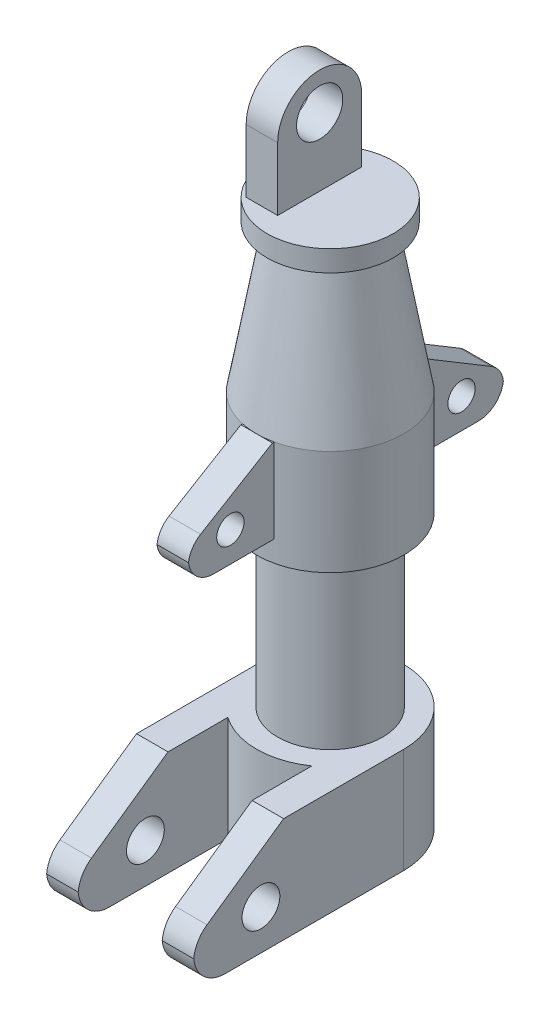
SolidWorks part; units mm, degrees
ref_plane "Front Plane" through (0, 0, 0) normal (0, 0, 1) x (1, 0, 0)
ref_plane "Top Plane" through (0, 0, 0) normal (0, 1, 0) x (1, 0, 0)
ref_plane "Right Plane" through (0, 0, 0) normal (1, 0, 0) x (0, 0, -1)
sketch "Sketch1" plane through (0, 0, 0) normal (0, 1, 0) x (1, 0, 0)
  circle A0 centre (0, 0) radius 35
  dimension "D1" = 70
ref_plane "Plane1" through (0, 50, 0) normal (0, 1, 0) x (1, 0, 0)
ref_plane "Plane2" through (0, 130, 0) normal (0, 1, 0) x (1, 0, 0)
ref_plane "Plane3" through (0, 180, 0) normal (0, 1, 0) x (1, 0, 0)
ref_plane "Plane4" through (0, 250, 0) normal (0, 1, 0) x (1, 0, 0)
extrude "Boss-Extrude1" add sketch "Sketch1" along normal blind 50 contours A0
sketch "Sketch6" plane through (0, 50, 0) normal (0, 1, 0) x (1, 0, 0)
  circle A0 centre (0, 0) radius 25
  dimension "D1" = 50
extrude "Boss-Extrude2" add sketch "Sketch6" along normal blind 80
sketch "Sketch7" plane through (0, 130, 0) normal (0, 1, 0) x (1, 0, 0)
  circle A0 centre (0, 0) radius 35
  dimension "D1" = 70
extrude "Boss-Extrude3" add sketch "Sketch7" along normal blind 50
ref_plane "Plane6" through (0, 250, 0) normal (0, 1, 0) x (1, 0, 0)
sketch "Sketch10" plane through (0, 250, 0) normal (0, 1, 0) x (1, 0, 0)
  circle A0 centre (0, 0) radius 30
  dimension "D1" = 60
extrude "Boss-Extrude5" add sketch "Sketch10" along normal blind 10 separate body
sketch "Sketch11" plane through (0, 0, 0) normal (1, 0, 0) x (0, 0, -1)
  line L0 (0, 250) -> (22.6571, 250)
  line L1 (-30, 250) -> (30, 250) construction
  line L2 (22.6571, 250) -> (35, 180)
  line L3 (35, 180) -> (0, 180)
  line L4 (35, 180) -> (-35, 180) construction
  line L5 (0, 180) -> (0, 250)
  dimension "D1" = 10
revolve "Revolve1" add sketch "Sketch11" angle 360 about L5
sketch "Sketch12" plane through (0, 0, 0) normal (0, -1, 0) x (1, 0, 0)
  line L0 (-35, 0) -> (-35, 100.0092)
  line L1 (-35, 100.0092) -> (35, 100.0092)
  line L2 (35, 100.0092) -> (35, 0)
  line L3 (35, 0) -> (-35, 0)
  circle A0 centre (0, 0) radius 35 construction
extrude "Boss-Extrude6" add sketch "Sketch12" against normal blind 50
sketch "Sketch13" plane through (-35, 0, 0) normal (-1, 0, 0) x (0, 0, 1)
  line L0 (57.1647, 50) -> (100.0092, 20)
  line L1 (100.0092, 50) -> (0, 50) construction
  line L2 (100.0092, 50) -> (100.0092, 0) construction
  line L4 (100.0092, 0) -> (0, 0) construction
  line L5 (57.1647, 50) -> (100.0092, 50)
  line L6 (100.0092, 50) -> (100.0092, 20)
  dimension "D1" = 35
  dimension "D2" = 20
extrude "Cut-Extrude1" cut sketch "Sketch13" against normal through all
sketch "Sketch14" plane through (0, 0, 0) normal (0, -1, 0) x (1, 0, 0)
  line L0 (-35, 100.0092) -> (-35, 0) construction
  line L1 (-20, 108.7406) -> (20, 108.7406)
  line L2 (-20, 108.7406) -> (-20, 28.7228)
  line L4 (20, 108.7406) -> (20, 28.7228)
  line L5 (35, 0) -> (35, 100.0092) construction
  arc A0 (20, 28.7228) -> (-20, 28.7228) centre (0, 0) ccw
  dimension "D1" = 70
  dimension "D2" = 15
  dimension "D3" = 15
extrude "Cut-Extrude2" cut sketch "Sketch14" against normal through all
fillet "Fillet1" radius 15 4 edges at (27.5, 0, 100.0092) (27.5, 20, 100.0092) (-27.5, 0, 100.0092) (-27.5, 20, 100.0092)
sketch "Sketch15" plane through (-35, 0, 0) normal (-1, 0, 0) x (0, 0, 1)
  line L0 (85.0092, 0) -> (0, 0) construction
  circle A0 centre (67.9433, 19) radius 9
  dimension "D1" = 18
  dimension "D2" = 19
  dimension "D3" = 32
extrude "Cut-Extrude3" cut sketch "Sketch15" against normal through all
sketch "Sketch16" plane through (0, 0, 0) normal (1, 0, 0) x (0, 0, -1)
  line L0 (-35, 180) -> (-75, 155.9656)
  line L1 (-75, 155.9656) -> (-75, 140)
  line L2 (-75, 140) -> (-35, 140)
  line L3 (-35, 180) -> (-35, 130) construction
  line L5 (-35, 130) -> (35, 130) construction
  line L6 (-35, 180) -> (0, 180)
  line L7 (-35, 180) -> (35, 180) construction
  line L8 (0, 180) -> (0, 140)
  line L9 (0, 140) -> (-35, 140)
  dimension "D3" = 31
  dimension "D1" = 10
  dimension "D2" = 75
extrude "Boss-Extrude8" add sketch "Sketch16" along normal blind 7.5 and the other way blind 7.5 contours L0 L1 L2 L9 L8 L6
fillet "Fillet2" radius 12 2 edges at (0, 140, 75) (0, 155.9656, 75)
sketch "Sketch17" plane through (7.5, 0, 0) normal (1, 0, 0) x (0, 0, -1)
  line L0 (-34.187, 140) -> (-63, 140) construction
  circle A0 centre (-55, 154.29) radius 6.5
  dimension "D1" = 13
  dimension "D2" = 14.29
  dimension "D3" = 55
extrude "Cut-Extrude4" cut sketch "Sketch17" against normal through all
mirror "Mirror1" about plane through (0, 0, 0) normal (0, 0, 1) of "Boss-Extrude8"
fillet "Fillet3" radius 12 2 edges at (0, 140, -75) (0, 155.9656, -75)
mirror "Mirror2" about plane through (0, 0, 0) normal (0, 0, 1) of "Cut-Extrude4"
sketch "Sketch18" plane through (0, 260, 0) normal (0, 1, 0) x (1, 0, 0)
  line L1 (-20, 20) -> (-5, 20)
  line L2 (-20, 20) -> (-20, -20)
  line L3 (-20, -20) -> (-5, -20)
  line L4 (-5, 20) -> (-5, -20)
  dimension "D1" = 15
  dimension "D2" = 5
  dimension "D3" = 40
  dimension "D4" = 20
extrude "Boss-Extrude9" add sketch "Sketch18" along normal blind 50
sketch "Sketch19" plane through (-20, 0, 0) normal (-1, 0, 0) x (0, 0, 1)
  line L0 (-20, 310) -> (20, 310) construction
  line L1 (-20, 290) -> (-20, 310)
  line L2 (-20, 310) -> (20, 310)
  line L3 (20, 310) -> (20, 290)
  arc A0 (20, 290) -> (-20, 290) centre (0, 290) ccw
  line M5 (20, 260) -> (20, 310)
  line M6 (20, 310) -> (-20, 310)
  line M7 (-20, 310) -> (-20, 260)
  dimension "D1" = 40
extrude "Cut-Extrude5" cut sketch "Sketch19" against normal through all contours A0 M5 M6 | A0 L2 M7 region at (-20, 305.5326, 15.5326) region at (-20, 305.5326, -15.5326)
sketch "Sketch20" plane through (-20, 0, 0) normal (-1, 0, 0) x (0, 0, 1)
  circle A0 centre (0, 292.4488) radius 11
  dimension "D1" = 22
extrude "Cut-Extrude6" cut sketch "Sketch20" against normal through all
sketch "Sketch21" plane through (0, 0, 0) normal (0, -1, 0) x (1, 0, 0)
  circle A0 centre (0, 0) radius 20
  dimension "D1" = 40
extrude "Cut-Extrude7" cut sketch "Sketch21" against normal blind 235
